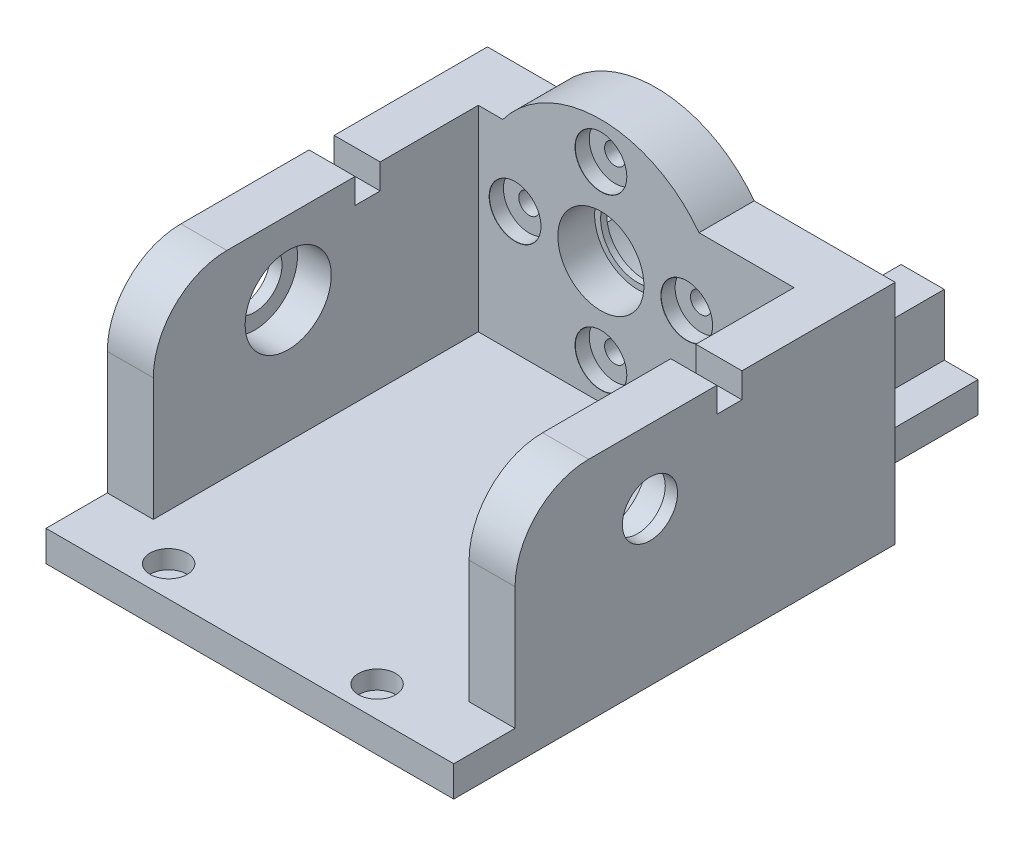
SolidWorks part; units mm, degrees
ref_plane "Front Plane" through (0, 0, 0) normal (0, 0, 1) x (1, 0, 0)
ref_plane "Top Plane" through (0, 0, 0) normal (0, 1, 0) x (1, 0, 0)
ref_plane "Right Plane" through (0, 0, 0) normal (1, 0, 0) x (0, 0, -1)
sketch "Sketch1" plane through (0, 0, 0) normal (0, 0, 1) x (1, 0, 0)
  circle A0 centre (0, 0) radius 7.025
  circle A1 centre (0, 0) radius 12
  dimension "D1" = 14.05
  dimension "D2" = 24
extrude "Boss-Extrude1" add sketch "Sketch1" along normal blind 3 and the other way blind 3 contours A1 | A0
ref_plane "Plane1" through (36.5, 0, 0) normal (1, 0, 0) x (0, 0, -1)
sketch "Sketch2" plane through (36.5, 0, 0) normal (1, 0, 0) x (0, 0, -1)
  circle A0 centre (-34, 0) radius 7.025
  circle A1 centre (-34, 0) radius 12
  dimension "D1" = 14.05
  dimension "D2" = 24
  dimension "D3" = 34
extrude "Boss-Extrude2" add sketch "Sketch2" against normal blind 5 and the other way blind 5 separate body
sketch "Sketch3" plane through (0, 0, 0) normal (0, 1, 0) x (1, 0, 0)
  line L0 (0, -3) -> (31.5, -3)
  line L1 (-12, -3) -> (12, -3) construction
  line L2 (31.5, -3) -> (31.5, -34)
  line L3 (31.5, -22) -> (31.5, -46) construction
  line L4 (31.5, -34) -> (41.5, -34)
  line L5 (41.5, -46) -> (41.5, -22) construction
  line L6 (41.5, -34) -> (41.5, 3)
  line L7 (41.5, 3) -> (0, 3)
  line L8 (7.025, 3) -> (-7.025, 3) construction
  line L9 (0, 3) -> (0, -3)
extrude "Boss-Extrude3" add sketch "Sketch3" along normal through all and the other way through all
sketch "Sketch4" plane through (0, 0, 3) normal (0, 0, 1) x (1, 0, 0)
  line L0 (0, 7.025) -> (0, -7.025) construction
  circle A0 centre (0, 0) radius 7.025
extrude "Cut-Extrude1" cut sketch "Sketch4" against normal through all
sketch "Sketch5" plane through (31.5, 0, 0) normal (-1, 0, 0) x (0, 0, 1)
  circle A0 centre (34, 0) radius 7.025
extrude "Cut-Extrude2" cut sketch "Sketch5" against normal through all
sketch "Sketch6" plane through (0, 0, -3) normal (0, 0, -1) x (-1, 0, 0)
  circle A0 centre (0, 0) radius 6.05
  circle A1 centre (0, 0) radius 12
  arc A2 (0, -12) -> (0, 12) centre (0, 0) ccw construction
  dimension "D1" = 12.1
extrude "Boss-Extrude4" add sketch "Sketch6" along normal blind 1 contours A1 | A0
sketch "Sketch7" plane through (0, 0, -3) normal (0, 0, -1) x (-1, 0, 0)
  line L0 (-20, 0) -> (-20, -20)
  line L1 (-20, -20) -> (20, -20)
  line L2 (20, -20) -> (20, 0)
  arc A0 (20, 0) -> (-20, 0) centre (0, 0) ccw
  circle A1 centre (0, 0) radius 11.35
  dimension "D1" = 22.7
  dimension "D2" = 40
  dimension "D3" = 20
extrude "Boss-Extrude5" add sketch "Sketch7" along normal blind 3
sketch "Sketch8" plane through (0, 0, -3) normal (0, 0, 1) x (1, 0, 0)
  circle A0 centre (0, 0) radius 20
  circle A1 centre (0, 0) radius 7.025
  dimension "D1" = 14.05
extrude "Boss-Extrude7" add sketch "Sketch8" along normal up to surface (6 mm away) up to face at (7.025, 0, 3)
hole_wizard "CBORE for M3 Hex Head Machine Screw1" positions "Sketch15" profile "Sketch10" counterbore size "M3" standard "ANSI Metric"
sketch "Sketch15" plane through (0, 0, 3) normal (0, 0, 1) x (1, 0, 0)
  circle A1 centre (0, 0) radius 14
  point P43 (0, 14)
  point P45 (0, -14)
  point P47 (14, 0)
  point P49 (-14, 0)
  dimension "D1" = 28
sketch "Sketch10" plane through (-14, 0, 3) normal (1, 0, 0) x (0, -1, 0)
  line L0 (0, 0) -> (0, 14.0215)
  line L1 (0, 14.0215) -> (1.7, 13)
  line L2 (1.7, 13) -> (1.7, 2.3)
  line L3 (1.7, 2.3) -> (4.2, 2.3)
  line L5 (4.2, 2.3) -> (4.2, 0.025)
  line L6 (4.2, 0.025) -> (4.225, 0)
  line L7 (4.225, 0) -> (0, 0)
  line L8 (-4.2, 0.025) -> (-4.225, 0) construction
  line L10 (0, 14.0215) -> (-1.7, 13) construction
  line L11 (0, -6.35) -> (0, 107.95) construction
  dimension "Hole Dia." = 3.4
  dimension "Hole Depth" = 13
  dimension "C'Bore Dia." = 8.4
  dimension "C'Bore Depth" = 2.3
  dimension "Near C'Sink Dia." = 8.45
  dimension "Near C'Sink Angle" = 90
  dimension "Drill Angle" = 118
sketch "Sketch14" plane through (0, 0, -6) normal (0, 0, -1) x (-1, 0, 0)
  line L3 (-20, 0) -> (-18, 0)
  line L4 (18, 0) -> (20, 0)
  line L6 (-20, 0) -> (-20, -20)
  line L7 (-20, -20) -> (20, -20)
  line L8 (20, -20) -> (20, 0)
  line L9 (-20, 0) -> (-20, -20)
  line L10 (-20, -20) -> (20, -20)
  line L11 (20, -20) -> (20, 0)
  arc A1 (-18, 0) -> (18, 0) centre (0, 0) ccw
  arc A2 (20, 0) -> (-20, 0) centre (0, 0) ccw
  dimension "D2" = 36
  dimension "D1" = 0
extrude "Boss-Extrude8" add sketch "Sketch14" along normal blind 45 contours L9 L10 L11 L4 A1 L3
sketch "Sketch16" plane through (0, 0, -51) normal (0, 0, -1) x (-1, 0, 0)
  line L10 (-18, 0) -> (-20, 0)
  line L11 (-20, 0) -> (-20, -20)
  line L12 (-20, -20) -> (20, -20)
  line L13 (20, -20) -> (20, 0)
  line L14 (20, 0) -> (18, 0)
  line L15 (-18.7, 0) -> (-20, 0)
  line L16 (-20, 0) -> (-20, -20)
  line L17 (-20, -20) -> (20, -20)
  line L18 (20, -20) -> (20, 0)
  line L19 (20, 0) -> (18.7, 0)
  arc A0 (-18.7, 0) -> (18.7, 0) centre (0, 0) ccw
  arc A3 (-18, 0) -> (18, 0) centre (0, 0) ccw
  dimension "D1" = 37.4
  dimension "D2" = 0
extrude "Boss-Extrude9" add sketch "Sketch16" along normal blind 35
sketch "Sketch17" plane through (0, -20, 0) normal (0, -1, 0) x (1, 0, 0)
  line L0 (-27.5, -3) -> (27.5, -3)
  line L1 (41.5, -3) -> (20, -3) construction
  line L2 (27.5, -3) -> (27.5, -86)
  line L3 (27.5, -86) -> (-27.5, -86)
  line L4 (-27.5, -86) -> (-27.5, -3)
  point P7 (0, -3)
  dimension "D1" = 55
extrude "Boss-Extrude10" add sketch "Sketch17" along normal blind 5
sketch "Sketch18" plane through (0, -25, 0) normal (0, -1, 0) x (1, 0, 0)
  line L0 (-27.5, -86) -> (27.5, -86) construction
  line L1 (-27.5, -3) -> (-20, -3)
  line L2 (-27.5, -3) -> (-27.5, -86)
  line L3 (-27.5, -86) -> (-20, -86)
  line L4 (-20, -3) -> (-20, -86)
  line L5 (27.5, -3) -> (20, -3)
  line L6 (27.5, -3) -> (27.5, -86)
  line L7 (27.5, -86) -> (20, -86)
  line L8 (20, -3) -> (20, -86)
  dimension "D1" = 7.5
extrude "Boss-Extrude11" add sketch "Sketch18" along normal blind 35
sketch "Sketch20" plane through (27.5, 0, 0) normal (1, 0, 0) x (0, 0, -1)
  line L0 (86, -20) -> (3, -20) construction
  line L2 (3, -60) -> (3, -20) construction
  circle A0 centre (23.75, -45) radius 4
  circle A1 centre (65.25, -45) radius 4
  dimension "D1" = 25
  dimension "D4" = 8
  dimension "D5" = 8
  dimension "D2" = 20.75
  dimension "D3" = 41.5
extrude "Cut-Extrude3" cut sketch "Sketch20" against normal through all
sketch "Sketch21" plane through (0, -12, 0) normal (0, -1, 0) x (1, 0, 0)
  line L7 (31.5, 34) -> (31.5, 46)
  line L8 (31.5, 46) -> (41.5, 46)
  line L9 (41.5, 46) -> (41.5, 34)
  line L14 (20, -3) -> (41.5, -3)
  line L15 (41.5, -3) -> (41.5, 34)
  line L16 (41.5, 34) -> (31.5, 34)
  line L17 (31.5, 34) -> (31.5, 3)
  line L18 (31.5, 3) -> (16, 3)
  line L19 (16, 3) -> (16, -3)
  line L20 (16, -3) -> (20, -3)
  line L21 (20, -3) -> (41.5, -3)
  line L22 (41.5, -3) -> (41.5, 34)
  line L24 (31.5, 34) -> (31.5, 3)
  line L25 (31.5, 3) -> (16, 3)
  line L26 (16, 3) -> (16, -3)
  line L27 (16, -3) -> (20, -3)
  dimension "D1" = 0
extrude "Boss-Extrude12" add sketch "Sketch21" along normal up to surface (13 mm away) up to face at (0, -25, -44.5)
sketch "Sketch23" plane through (0, -12, 0) normal (0, 1, 0) x (1, 0, 0)
  line L8 (41.5, -46) -> (41.5, -34)
  line L9 (41.5, -34) -> (31.5, -34)
  line L10 (31.5, -34) -> (31.5, -46)
  line L11 (31.5, -46) -> (41.5, -46)
  line L12 (41.5, -46) -> (41.5, -34)
  line L13 (41.5, -34) -> (31.5, -34)
  line L14 (31.5, -34) -> (31.5, -46)
  line L15 (31.5, -46) -> (41.5, -46)
  dimension "D1" = 0
extrude "Boss-Extrude14" add sketch "Sketch23" along normal up to next
sketch "Sketch24" plane through (0, 0, -3) normal (0, 0, 1) x (1, 0, 0)
  line L7 (20, -60) -> (27.5, -60)
  line L8 (27.5, -60) -> (27.5, -25)
  line L9 (27.5, -25) -> (20, -25)
  line L10 (20, -25) -> (20, -60)
  line L14 (16, -25) -> (16, -12)
  line L15 (-20, 0) -> (-20, -20)
  line L16 (-20, -20) -> (-27.5, -20)
  line L17 (-27.5, -20) -> (-27.5, -60)
  line L18 (-27.5, -60) -> (-20, -60)
  line L19 (-20, -60) -> (-20, -25)
  line L20 (-20, -25) -> (16, -25)
  line L21 (16, -25) -> (16, -12)
  line L22 (-20, 0) -> (-20, -20)
  line L23 (-20, -20) -> (-27.5, -20)
  line L24 (-27.5, -20) -> (-27.5, -60)
  line L25 (-27.5, -60) -> (-20, -60)
  line L26 (-20, -60) -> (-20, -25)
  line L27 (-20, -25) -> (16, -25)
  arc A2 (-20, 0) -> (16, -12) centre (0, 0) ccw
  arc A3 (-20, 0) -> (16, -12) centre (0, 0) ccw
  dimension "D1" = 0
extrude "Boss-Extrude15" add sketch "Sketch24" along normal up to surface (6 mm away) up to face at (4.225, 14, 3)
sketch "Sketch25" plane through (0, 0, 3) normal (0, 0, 1) x (1, 0, 0)
  line L0 (-27.5, -20) -> (31.5, -20)
  line L1 (31.5, -25) -> (31.5, 0) construction
  line L2 (31.5, -20) -> (31.5, -25)
  line L3 (31.5, -25) -> (-27.5, -25)
  line L4 (-27.5, -20) -> (-27.5, -60) construction
  line L5 (-27.5, -20) -> (-27.5, -25)
extrude "Boss-Extrude16" add sketch "Sketch25" along normal up to surface (43 mm away) up to face at (36.5, -12.5, 46)
sketch "Sketch26" plane through (-20, 0, 0) normal (-1, 0, 0) x (0, 0, 1)
  line L0 (34, 12) -> (-6, 12)
  line L1 (-6, 20) -> (-6, 0) construction
  line L2 (-6, 12) -> (-6, -20)
  line L3 (46, -20) -> (-86, -20) construction
  line L4 (-6, -20) -> (46, -20)
  line L6 (34, 12) -> (46, 12)
  line L7 (46, 12) -> (56, 12)
  line L8 (56, 12) -> (56, -20)
  line L9 (56, -20) -> (46, -20)
  circle A1 centre (34, 0) radius 7.025
  dimension "D1" = 10
  dimension "D2" = 14.05
extrude "Boss-Extrude17" add sketch "Sketch26" along normal up to surface (7.5 mm away)
sketch "Sketch27" plane through (-20, 0, 0) normal (1, 0, 0) x (0, 0, -1)
  line L0 (6, 0) -> (6, 12)
  line L1 (6, 12) -> (-3, 12)
  line L2 (-3, 12) -> (-3, 0)
  line L3 (-3, 20) -> (-3, 0) construction
  line L4 (6, 0) -> (-3, 0)
extrude "Boss-Extrude18" add sketch "Sketch27" along normal up to next
sketch "Sketch28" plane through (-27.5, 0, 0) normal (-1, 0, 0) x (0, 0, 1)
  line L0 (46, -25) -> (3, -60)
  line L1 (3, -60) -> (3, -25)
  line L2 (3, -25) -> (46, -25)
extrude "Boss-Extrude19" add sketch "Sketch28" against normal blind 7.5
mirror "Mirror1" about plane through (0, 0, 0) normal (1, 0, 0) of "Boss-Extrude19"
sketch "Sketch29" plane through (20, 0, 0) normal (1, 0, 0) x (0, 0, -1)
  line L10 (3, 0) -> (3, -20)
  line L11 (3, -20) -> (86, -20)
  line L12 (86, -20) -> (86, 0)
  line L13 (86, 0) -> (6, 0)
  line L14 (6, 0) -> (3, 0)
  line L15 (3, 0) -> (3, -20)
  line L16 (3, -20) -> (86, -20)
  line L17 (86, -20) -> (86, 0)
  line L18 (86, 0) -> (6, 0)
  line L19 (6, 0) -> (3, 0)
  dimension "D1" = 0
extrude "Boss-Extrude20" add sketch "Sketch29" along normal blind 2
mirror "Mirror2" about plane through (0, 0, 0) normal (1, 0, 0) of "Boss-Extrude20"
sketch "Sketch30" plane through (22, 0, 0) normal (1, 0, 0) x (0, 0, -1)
  line L0 (16, 0) -> (16, -10)
  line L1 (86, 0) -> (3, 0) construction
  line L2 (16, -10) -> (21, -10)
  line L3 (21, -10) -> (21, 0)
  line L4 (21, 0) -> (16, 0)
  line L5 (6, 0) -> (6, 20) construction
  dimension "D1" = 10
  dimension "D2" = 5
  dimension "D3" = 10
extrude "Cut-Extrude4" cut sketch "Sketch30" against normal through all
pattern_linear "LPattern2" count 5 spacing 15 along (0, 0, -1) of "Cut-Extrude4"
sketch "Sketch35" plane through (41.5, 0, 0) normal (1, 0, 0) x (0, 0, -1)
  line L0 (3, 12) -> (6, 12)
  line L1 (6, 12) -> (6, -25)
  line L2 (6, -25) -> (3, -25)
  line L3 (3, -25) -> (3, 12)
extrude "Boss-Extrude25" add sketch "Sketch35" against normal up to next
sketch "Sketch36" plane through (0, 0, 46) normal (0, 0, 1) x (1, 0, 0)
  line L10 (41.5, 12) -> (31.5, 12)
  line L20 (31.5, 0) -> (31.5, -20)
  line L21 (31.5, -20) -> (-20, -20)
  line L22 (-20, -20) -> (-27.5, -20)
  line L23 (-27.5, -20) -> (-27.5, -25)
  line L24 (-27.5, -25) -> (-20, -25)
  line L25 (-20, -25) -> (20, -25)
  line L26 (20, -25) -> (27.5, -25)
  line L27 (27.5, -25) -> (41.5, -25)
  line L28 (41.5, -25) -> (41.5, 0)
  line L29 (41.5, 0) -> (31.5, 0)
  line L30 (31.5, 12) -> (31.5, -20)
  line L31 (31.5, -20) -> (-20, -20)
  line L32 (-20, -20) -> (-27.5, -20)
  line L33 (-27.5, -20) -> (-27.5, -25)
  line L34 (-27.5, -25) -> (-20, -25)
  line L35 (-20, -25) -> (20, -25)
  line L36 (20, -25) -> (27.5, -25)
  line L37 (27.5, -25) -> (41.5, -25)
  line L38 (41.5, -25) -> (41.5, 12)
  dimension "D1" = 0
extrude "Boss-Extrude26" add sketch "Sketch36" along normal up to surface (10 mm away) up to face at (-23.75, -4, 56)
sketch "Sketch37" plane through (0, 0, 46) normal (0, 0, -1) x (-1, 0, 0)
  line L8 (-41.5, 12) -> (-41.5, 0)
  line L9 (-41.5, 0) -> (-31.5, 0)
  line L10 (-31.5, 0) -> (-31.5, 12)
  line L11 (-31.5, 12) -> (-41.5, 12)
  line L12 (-41.5, 12) -> (-41.5, 0)
  line L13 (-41.5, 0) -> (-31.5, 0)
  line L14 (-31.5, 0) -> (-31.5, 12)
  line L15 (-31.5, 12) -> (-41.5, 12)
  dimension "D1" = 0
extrude "Boss-Extrude27" add sketch "Sketch37" along normal up to next
fillet "Fillet5" radius 12 2 edges at (36.5, 12, 56) (-23.75, 12, 56)
sketch "Sketch40" plane through (0, 0, 56) normal (0, 0, 1) x (1, 0, 0)
  line L0 (-27.5, -20) -> (41.5, -20)
  line L1 (-27.5, 0) -> (-27.5, -25) construction
  line L2 (41.5, 0) -> (41.5, -25) construction
  line L3 (41.5, -20) -> (41.5, -25)
  line L4 (41.5, -25) -> (-27.5, -25)
  line L5 (-27.5, -25) -> (-27.5, -20)
extrude "Boss-Extrude29" add sketch "Sketch40" along normal blind 10
sketch "Sketch41" plane through (0, -20, 0) normal (0, 1, 0) x (1, 0, 0)
  line L1 (-27.5, -66) -> (-27.5, -56) construction
  line L2 (41.5, -66) -> (41.5, -56) construction
  line L3 (41.5, -66) -> (-27.5, -66) construction
  circle A0 centre (-12.5, -61) radius 3.025
  circle A1 centre (21.5, -61) radius 3.025
  dimension "D1" = 6.05
  dimension "D2" = 6.05
  dimension "D3" = 15
  dimension "D4" = 20
  dimension "D5" = 5
extrude "Cut-Extrude6" cut sketch "Sketch41" against normal blind 3
sketch "Sketch42" plane through (0, 12, 0) normal (0, 1, 0) x (1, 0, 0)
  line L0 (-27.5, 6) -> (-27.5, -44) construction
  line L1 (-27.5, -19) -> (-20, -19)
  line L2 (-27.5, -19) -> (-27.5, -23.1)
  line L3 (-27.5, -23.1) -> (-20, -23.1)
  line L4 (-20, -19) -> (-20, -23.1)
  line L5 (-20, -3) -> (-20, -56) construction
  line L6 (31.5, -56) -> (31.5, -3) construction
  line L7 (31.5, -19) -> (41.5, -19)
  line L8 (31.5, -19) -> (31.5, -23.1)
  line L9 (31.5, -23.1) -> (41.5, -23.1)
  line L10 (41.5, -19) -> (41.5, -23.1)
  line L11 (41.5, -44) -> (41.5, 6) construction
  line L12 (-27.5, 6) -> (-16, 6) construction
  line L13 (16, 6) -> (41.5, 6) construction
  dimension "D1" = 4.1
  dimension "D2" = 4.1
  dimension "D3" = 25
  dimension "D4" = 25
extrude "Cut-Extrude7" cut sketch "Sketch42" against normal blind 4.1
sketch "Sketch43" plane through (0, -25, 0) normal (0, -1, 0) x (1, 0, 0)
  line L1 (-37.1369, 70.3008) -> (57.5439, 70.3008)
  line L2 (-37.1369, 70.3008) -> (-37.1369, -93.4331)
  line L3 (-37.1369, -93.4331) -> (57.5439, -93.4331)
  line L4 (57.5439, 70.3008) -> (57.5439, -93.4331)
extrude "Cut-Extrude8" cut sketch "Sketch43" along normal through all
sketch "Sketch44" plane through (0, 0, -86) normal (0, 0, -1) x (-1, 0, 0)
  line L1 (-28.2301, 4.4041) -> (28.6423, 4.4041)
  line L2 (-28.2301, 4.4041) -> (-28.2301, -28.4766)
  line L3 (-28.2301, -28.4766) -> (28.6423, -28.4766)
  line L4 (28.6423, 4.4041) -> (28.6423, -28.4766)
extrude "Cut-Extrude9" cut sketch "Sketch44" against normal up to surface (55 mm away) up to face at (-19.4271, -5.0562, -31)
sketch "Sketch45" plane through (41.5, 0, 0) normal (1, 0, 0) x (0, 0, -1)
  line L1 (-75.844, 19.2649) -> (18.5876, 19.2649)
  line L2 (-75.844, 19.2649) -> (-75.844, -31.2156)
  line L3 (-75.844, -31.2156) -> (18.5876, -31.2156)
  line L4 (18.5876, 19.2649) -> (18.5876, -31.2156)
extrude "Cut-Extrude10" cut sketch "Sketch45" against normal blind 2.5
sketch "Sketch46" plane through (39, 0, 0) normal (1, 0, 0) x (0, 0, -1)
  circle A0 centre (-34, 0) radius 7.025
  circle A1 centre (-34, 0) radius 4.5
  dimension "D1" = 9
  dimension "D2" = 14.05
extrude "Boss-Extrude30" add sketch "Sketch46" against normal blind 2
sketch "Sketch47" plane through (-27.5, 0, 0) normal (-1, 0, 0) x (0, 0, 1)
  circle A0 centre (34, 0) radius 7.025
  circle A1 centre (34, 0) radius 4.5
extrude "Boss-Extrude31" add sketch "Sketch47" against normal blind 2
sketch "Sketch48" plane through (0, 0, 0) normal (0, 1, 0) x (1, 0, 0)
  line L1 (-22, 6) -> (22, 6)
  line L2 (-22, 6) -> (-22, 31)
  line L3 (-22, 31) -> (22, 31)
  line L4 (22, 6) -> (22, 31)
extrude "Cut-Extrude11" cut sketch "Sketch48" against normal up to surface (10 mm away) up to face at (18.4833, -10, -18.5)
